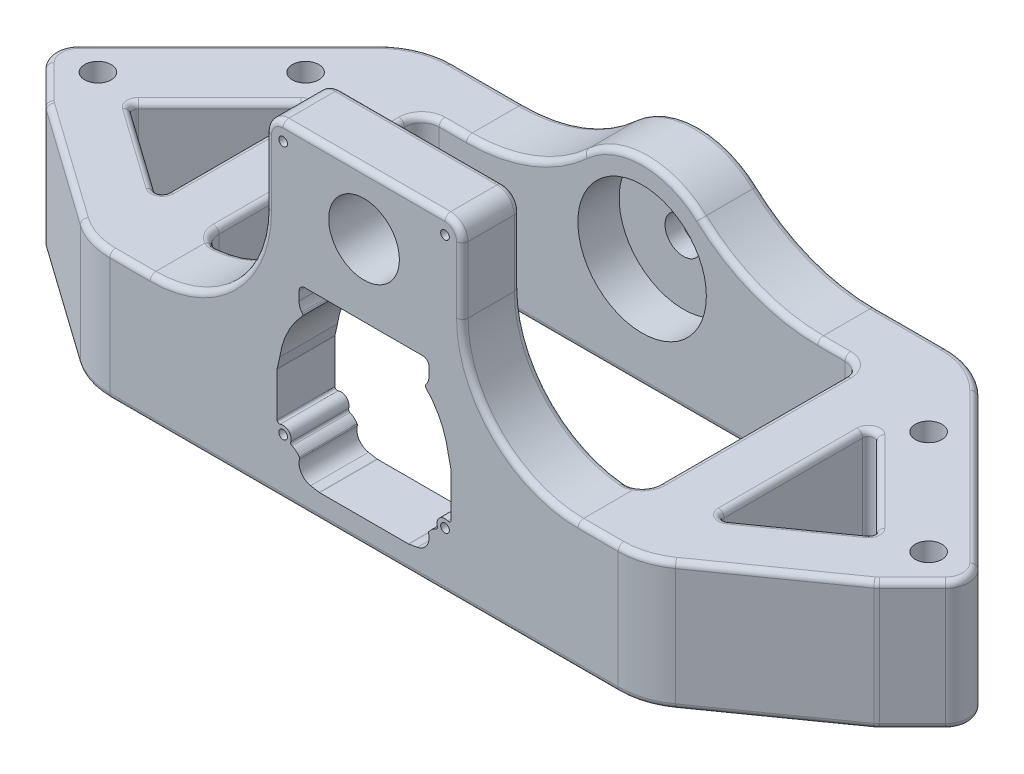
SolidWorks part; units mm, degrees
ref_plane "Front Plane" through (0, 0, 0) normal (0, 0, 1) x (1, 0, 0)
ref_plane "Top Plane" through (0, 0, 0) normal (0, 1, 0) x (1, 0, 0)
ref_plane "Right Plane" through (0, 0, 0) normal (1, 0, 0) x (0, 0, -1)
sketch "Sketch1" plane through (0, 0, 0) normal (0, 1, 0) x (1, 0, 0)
  line L0 (-48.1, -29.05) -> (-48.1, 29.05)
  line L1 (38.1, -19.05) -> (-38.1, -19.05)
  line L2 (38.1, -19.05) -> (38.1, 19.05)
  line L3 (38.1, 19.05) -> (-38.1, 19.05)
  line L4 (-38.1, -19.05) -> (-38.1, 19.05)
  line L5 (38.1, -19.05) -> (-38.1, 19.05) construction
  line L6 (38.1, 19.05) -> (-38.1, -19.05) construction
  line L11 (48.1, 29.05) -> (-48.1, 29.05)
  line L12 (48.1, -29.05) -> (48.1, 29.05)
  line L13 (48.1, -29.05) -> (-48.1, -29.05)
  line L14 (-48.1, 29.05) -> (-80.6068, -3.4568)
  line L15 (-80.6068, -3.4568) -> (-71.842, -12.2215)
  line L16 (-71.842, -12.2215) -> (-48.1, 11.5205)
  line L17 (0, 0) -> (0, 65.6417) construction
  line L18 (-76.3322, -7.7314) -> (0, 68.6008) construction
  line L19 (48.1, 29.05) -> (80.6068, -3.4568)
  line L20 (80.6068, -3.4568) -> (71.842, -12.2215)
  line L21 (71.842, -12.2215) -> (48.1, 11.5205)
  line L22 (-48.1, -29.05) -> (-71.842, -12.2215)
  line L23 (-48.1, -16.7927) -> (-64.669, -5.0485)
  line L24 (48.1, -29.05) -> (71.842, -12.2215)
  line L25 (48.1, -16.7927) -> (64.669, -5.0485)
  line L26 (-76.3322, -7.7314) -> (-269.4077, -200.8069) construction
  circle A0 centre (-71.842, -3.2413) radius 2.3
  circle A1 centre (-53.8815, 14.7193) radius 2.3
  circle A2 centre (53.8815, 14.7193) radius 2.3
  circle A3 centre (71.842, -3.2413) radius 2.3
  point P0 (0, 0)
  point P32 (-197.5656, -128.9648)
  point P34 (-215.5261, -146.9254)
  point P35 (0, 0)
  dimension "D10" = 4.6
  dimension "D1" = 10
  dimension "D2" = 45
  dimension "D3" = 12.3952
  dimension "D4" = 107.95
  dimension "D5" = 6.35
  dimension "D6" = 6.35
  dimension "D7" = 25.4
  dimension "D8" = 76.2
  dimension "D9" = 38.1
  dimension "D11" = 10
  dimension "D12" = 381
  dimension "D13" = 101.6
  dimension "D14" = 177.8
  dimension "D15" = 25.4
  dimension "D16" = 228.6
extrude "Boss-Extrude1" add sketch "Sketch1" along normal blind 22.25 contours L13 L12 L11 L0 L1 L4 L3 L2 | L15 L16 L0 L14 A1 A0 | L21 L20 L19 L12 A2 A3 | L0 L23 L16 L22 | L25 L12 L24 L21 region at (-58.2841, 0, 16.0663) region at (-46.9762, 0, 22.9214) region at (58.2841, 0, 16.0663) region at (-62.2337, 0, -6.6242) region at (62.2337, 0, -6.6242)
extrude "Boss-Extrude2" add sketch "Sketch1<3>" along normal blind 15.85 from surface contours L13 L12 L11 L0 L1 L4 L3 L2 region at (-46.9762, 0, 22.9214) starting at face at (53.623, 22.25, 3.4402)
sketch "Sketch1<3>" plane through (0, 0, 0) normal (0, 1, 0) x (1, 0, 0) same geometry as "Sketch1"
sketch "Sketch3" plane through (0, 0, 29.05) normal (0, 0, 1) x (1, 0, 0)
  line L0 (0, 0) -> (0, 38.1) construction
  line L1 (-48.1, 38.1) -> (48.1, 38.1) construction
  line L2 (7.7467, 4.2612) -> (9.2383, 4.5242)
  line L3 (-7.6773, 4.2551) -> (7.6773, 4.2551)
  line L4 (-9.2383, 4.5242) -> (-7.7467, 4.2612)
  line L5 (-15.0449, 19.0418) -> (-15.0449, 11.4779)
  line L6 (-14.5827, 21.1094) -> (-15.0348, 19.1309)
  line L7 (-10.7806, 29.7585) -> (-10.65, 29.5787)
  line L8 (-6.6626, 32.35) -> (-6.853, 32.6121)
  line L9 (6.853, 32.6121) -> (6.6626, 32.35)
  line L10 (10.65, 29.5787) -> (10.7806, 29.7585)
  line L11 (15.0348, 19.1309) -> (14.5827, 21.1094)
  line L12 (15.0449, 11.4779) -> (15.0449, 19.0418)
  line L13 (-48.1, 22.25) -> (-17, 22.25)
  line L14 (-17, 22.25) -> (-17, 56.7)
  line L15 (-17, 56.7) -> (17, 56.7)
  line L16 (17, 56.7) -> (17, 22.25)
  line L17 (17, 22.25) -> (48.1, 22.25)
  line L18 (48.1, 38.1) -> (48.1, 22.25) construction
  line L19 (48.1, 22.25) -> (48.1, 38.1)
  line L20 (48.1, 38.1) -> (17, 38.1)
  line L21 (-17, 38.1) -> (-48.1, 38.1)
  line L22 (-48.1, 38.1) -> (-48.1, 22.25)
  line L23 (-17, 38.1) -> (17, 38.1)
  line L24 (-11.2442, 31.1853) -> (-11.2442, 33.6774)
  line L25 (-11.2442, 33.6774) -> (11.1927, 33.6774)
  line L26 (11.1927, 33.6774) -> (11.2442, 31.1853)
  circle A0 centre (14, 9.8) radius 0.75
  circle A1 centre (-14, 9.8) radius 0.75
  circle A2 centre (-14, 53.7) radius 0.75
  circle A3 centre (14, 53.7) radius 0.75
  circle A4 centre (0, 46.05) radius 6.114
  arc A5 (12.4458, 8.8644) -> (11.1887, 7.8314) centre (13.5, 6.3) ccw
  arc A6 (9.2383, 4.5242) -> (11.1504, 7.5831) centre (8.8168, 6.9147) ccw
  arc A7 (7.6773, 4.2551) -> (7.7467, 4.2612) centre (7.6773, 4.6551) ccw
  arc A8 (-7.7467, 4.2612) -> (-7.6773, 4.2551) centre (-7.6773, 4.6551) ccw
  arc A9 (-11.1504, 7.5831) -> (-9.2383, 4.5242) centre (-8.8168, 6.9147) ccw
  arc A10 (-11.1887, 7.8314) -> (-12.4458, 8.8644) centre (-13.5, 6.3) ccw
  arc A11 (-12.6734, 9.3602) -> (-14.5014, 11.1045) centre (-14, 9.8) ccw
  arc A12 (-15.0348, 19.1309) -> (-15.0449, 19.0418) centre (-14.6449, 19.0418) ccw
  arc A13 (-10.6753, 29.1957) -> (-14.5827, 21.1094) centre (0, 19.05) ccw
  arc A14 (-6.853, 32.6121) -> (-10.7806, 29.7585) centre (-8.8168, 31.1853) ccw
  arc A15 (6.2909, 32.2555) -> (-6.2909, 32.2555) centre (0, 19.05) ccw
  arc A16 (10.7806, 29.7585) -> (6.853, 32.6121) centre (8.8168, 31.1853) ccw
  arc A17 (14.5827, 21.1094) -> (10.6753, 29.1957) centre (0, 19.05) ccw
  arc A18 (15.0449, 19.0418) -> (15.0348, 19.1309) centre (14.6449, 19.0418) ccw
  arc A19 (14.5014, 11.1045) -> (12.6734, 9.3602) centre (14, 9.8) ccw
  spline S0 degree 3 poles (12.4458, 8.8644) (12.5392, 8.9027) (12.6157, 8.9767) (12.699, 9.1584) (12.7052, 9.2644) (12.6734, 9.3602) knots 0 0 0 0 0.000302 0.000302 0.000604 0.000604 0.000604 0.000604 weights 1 1 1 1 1 1
  spline S1 degree 3 poles (11.1504, 7.5831) (11.1264, 7.6668) (11.1406, 7.7587) (11.1887, 7.8314) knots 0 0 0 0 0.000258 0.000258 0.000258 0.000258 weights 1 1 1 1
  spline S2 degree 3 poles (-11.1887, 7.8314) (-11.1406, 7.7587) (-11.1264, 7.6668) (-11.1504, 7.5831) knots 0 0 0 0 0.000258 0.000258 0.000258 0.000258 weights 1 1 1 1
  spline S3 degree 3 poles (-12.6734, 9.3602) (-12.7052, 9.2644) (-12.699, 9.1582) (-12.6155, 8.9765) (-12.5392, 8.9027) (-12.4458, 8.8644) knots 0 0 0 0 0.000302 0.000302 0.000604 0.000604 0.000604 0.000604 weights 1 1 1 1 1 1
  spline S4 degree 3 poles (-15.0449, 11.4779) (-15.0449, 11.3476) (-14.9779, 11.2213) (-14.7643, 11.0748) (-14.6231, 11.0578) (-14.5014, 11.1045) knots 0 0 0 0 0.000388 0.000388 0.000776 0.000776 0.000776 0.000776 weights 1 1 1 1 1 1
  spline S5 degree 3 poles (-10.65, 29.5787) (-10.6088, 29.522) (-10.5888, 29.4526) (-10.5979, 29.3131) (-10.627, 29.2466) (-10.6753, 29.1957) knots 0 0 0 0 0.000207 0.000207 0.000415 0.000415 0.000415 0.000415 weights 1 1 1 1 1 1
  spline S6 degree 3 poles (-6.2909, 32.2555) (-6.3541, 32.2254) (-6.4259, 32.2184) (-6.5613, 32.2528) (-6.6214, 32.2934) (-6.6626, 32.35) knots 0 0 0 0 0.000207 0.000207 0.000414 0.000414 0.000414 0.000414 weights 1 1 1 1 1 1
  spline S7 degree 3 poles (6.6626, 32.35) (6.6214, 32.2934) (6.5617, 32.2529) (6.4263, 32.2184) (6.3541, 32.2254) (6.2909, 32.2555) knots 0 0 0 0 0.000207 0.000207 0.000414 0.000414 0.000414 0.000414 weights 1 1 1 1 1 1
  spline S8 degree 3 poles (10.6753, 29.1957) (10.627, 29.2466) (10.598, 29.3127) (10.5887, 29.4522) (10.6088, 29.522) (10.65, 29.5787) knots 0 0 0 0 0.000207 0.000207 0.000415 0.000415 0.000415 0.000415 weights 1 1 1 1 1 1
  spline S9 degree 3 poles (14.5014, 11.1045) (14.6231, 11.0578) (14.765, 11.075) (14.9783, 11.2218) (15.0449, 11.3476) (15.0449, 11.4779) knots 0 0 0 0 0.000388 0.000388 0.000776 0.000776 0.000776 0.000776 weights 1 1 1 1 1 1
  point P5 (0, 19.05)
  point P17 (0, 19.05)
  point P86 (0, 33.6774)
  line M46 (48.1, 22.25) -> (48.1, 38.1)
  line M47 (48.1, 38.1) -> (-48.1, 38.1)
  line M48 (-48.1, 38.1) -> (-48.1, 22.25)
  dimension "D1" = 1.5
  dimension "D2" = 3
  dimension "D3" = 3
  dimension "D4" = 3
extrude "Boss-Extrude3" add sketch "Sketch3" against normal up to surface (10 mm away) contours L16 L15 L14 L23 A4 A3 A2 M47 region at (-16.6124, 47.4, 29.05) up to face at (0, 19.05, 19.05)
extrude "Cut-Extrude1" cut sketch "Sketch3<3>" against normal up to next contours L13 L14 M47 M48 | L16 L17 M46 M47 region at (-32.55, 30.175, 29.05) region at (32.55, 30.175, 29.05)
sketch "Sketch3<3>" plane through (0, 0, 29.05) normal (0, 0, 1) x (1, 0, 0) same geometry as "Sketch3"
extrude "Cut-Extrude2" cut sketch "Sketch3<4>" against normal up to next contours L3 L0 A15 S6 L8 A14 L7 S5 A13 L6 A12 L5 S4 A11 S3 A10 S2 A9 L4 A8 | L0 L3 A7 L2 A6 S1 A5 S0 A19 S9 L12 A18 L11 A17 S8 L10 A16 L9 S7 A15 | A1 | A0 | S6 A15 L25 L24 A14 L8 | S7 L9 A16 L26 L25 A15 region at (-6.6584, 18.6234, 29.05) region at (6.6584, 18.6234, 29.05) region at (-6.742, 33.2078, 29.05) region at (6.692, 33.2118, 29.05) region at (14, 9.8, 29.05) region at (-14, 9.8, 29.05)
sketch "Sketch3<4>" plane through (0, 0, 29.05) normal (0, 0, 1) x (1, 0, 0) same geometry as "Sketch3"
sketch "Sketch4" plane through (0, 0, -29.05) normal (0, 0, -1) x (-1, 0, 0)
  line L0 (0, 0) -> (0, 38.1) construction
  line L1 (17, 38.1) -> (-17, 38.1) construction
  line L5 (-17, 22.25) -> (-14.6547, 22.25)
  line L6 (-17, 22.25) -> (-17, 38.1)
  line L7 (-17, 38.1) -> (17, 38.1)
  line L8 (17, 38.1) -> (17, 22.25)
  line L9 (17, 22.25) -> (14.6547, 22.25)
  circle A0 centre (0, 19.05) radius 3.175
  circle A1 centre (0, 19.05) radius 15
  line M7 (17, 22.25) -> (17, 38.1)
  line M8 (17, 38.1) -> (-17, 38.1)
  line M9 (-17, 38.1) -> (-17, 22.25)
  dimension "D1" = 30
  dimension "D2" = 6.35
extrude "Cut-Extrude3" cut sketch "Sketch4" against normal up to next contours A1 L0 L7 L5 M9 | L0 A1 L9 M7 M8 | L0 A0 | A0 L0 region at (1.3475, 19.05, -29.05) region at (-1.3475, 19.05, -29.05) region at (10.8276, 32.9317, -29.05) region at (-10.8276, 32.9317, -29.05)
fillet "Fillet1" radius 20 2 edges at (17, 22.25, 24.05) (-17, 22.25, 24.05)
fillet "Fillet2" radius 3 2 edges at (-17, 56.7, 24.05) (17, 56.7, 24.05)
fillet "Fillet3" radius 1 2 edges at (11.1927, 33.6774, 24.05) (-11.2442, 33.6774, 24.05)
fillet "Fillet4" radius 1 6 edges at (48.1, 11.125, -11.5205) (-48.1, 11.125, -11.5205) (48.1, 11.125, 16.7927) (64.669, 11.125, 5.0485) (-48.1, 11.125, 16.7927) (-64.669, 11.125, 5.0485)
fillet "Fillet5" radius 3 4 edges at (-38.1, 11.125, -19.05) (38.1, 11.125, -19.05) (38.1, 11.125, 19.05) (-38.1, 11.125, 19.05)
fillet "Fillet6" radius 13 4 edges at (48.1, 11.125, -29.05) (-48.1, 11.125, -29.05) (-48.1, 11.125, 29.05) (48.1, 11.125, 29.05)
fillet "Fillet7" radius 4 4 edges at (80.6068, 11.125, 3.4568) (-80.6068, 11.125, 3.4568) (71.842, 11.125, 12.2215) (-71.842, 11.125, 12.2215)
sketch "Sketch5" plane through (0, 0, -19.05) normal (0, 0, 1) x (1, 0, 0)
  circle A0 centre (0, 19.05) radius 11.1125
  dimension "D1" = 22.225
extrude "Cut-Extrude4" cut sketch "Sketch5" against normal blind 7.1374
fillet "Fillet8" radius 30 2 edges at (14.6547, 22.25, -24.05) (-14.6547, 22.25, -24.05)
fillet "Fillet9" radius 1 8 edges at (56.8192, 0, -2.8014) (56.8192, 22.25, -2.8014) (-48.1, 22.25, 2.8759) (-48.1, 0, 2.8759) (-38.1, 0, 0) (-22.2014, 28.7964, 19.05) (0, 0, -29.05) (-64.843, 22.25, -12.307)
